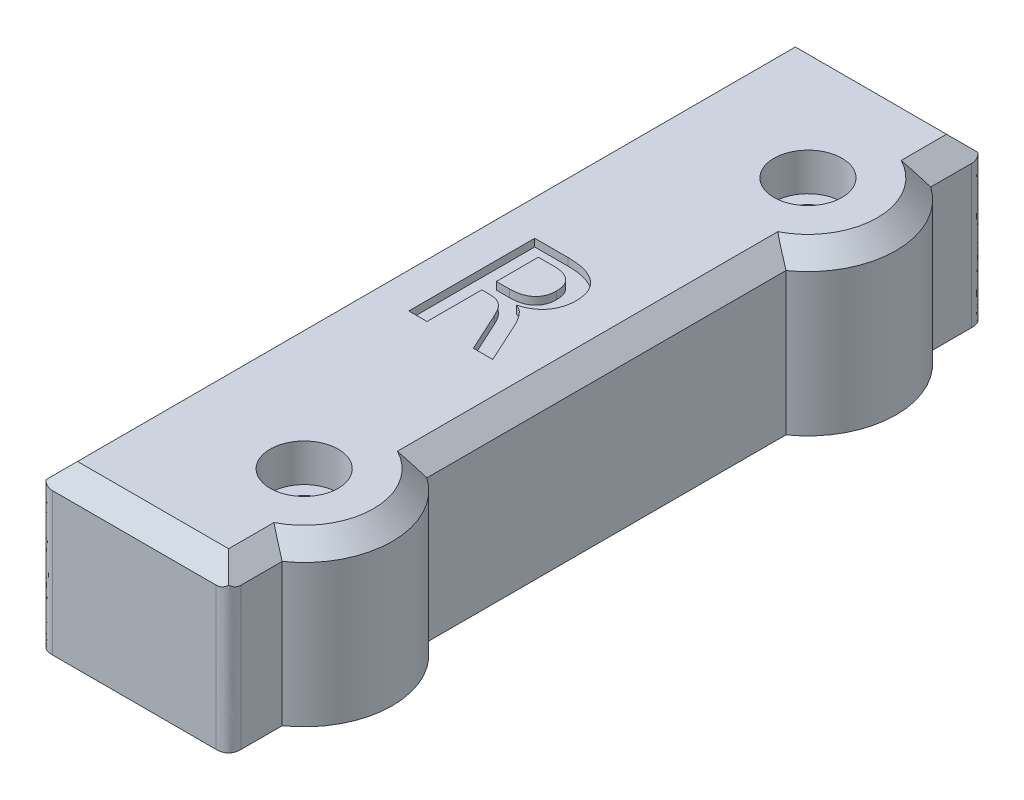
SolidWorks part; units mm, degrees
ref_plane "Front Plane" through (0, 0, 0) normal (0, 0, 1) x (1, 0, 0)
ref_plane "Top Plane" through (0, 0, 0) normal (0, 1, 0) x (1, 0, 0)
ref_plane "Right Plane" through (0, 0, 0) normal (1, 0, 0) x (0, 0, -1)
sketch "Sketch1" plane through (0, 0, 0) normal (0, 1, 0) x (1, 0, 0)
  line L0 (-1.3042, 0) -> (2.0884, 0) construction
  line L1 (0, -3.051) -> (0, -13.887) construction
  line L2 (7.5, 20) -> (-7.5, 20) construction
  line L3 (7.5, -30) -> (-7.5, -30)
  line L4 (7.5, -30) -> (7.5, 30)
  line L5 (7.5, 30) -> (-7.5, 30)
  line L6 (-7.5, -30) -> (-7.5, 30)
  line L7 (7.5, -30) -> (-7.5, 30) construction
  line L8 (7.5, 30) -> (-7.5, -30) construction
  line L9 (7.5, -20) -> (-7.5, -20) construction
  circle A6 centre (3.5, 20) radius 1.65
  circle A7 centre (3.5, -20) radius 1.65
  point P3 (0, 0)
  dimension "D4" = 3.3
  dimension "D1" = 10
  dimension "D2" = 40
  dimension "D3" = 15
  dimension "D5" = 4
extrude "Boss-Extrude1" add sketch "Sketch1" along normal blind 12.8
sketch "Sketch5" plane through (0, 0, 0) normal (0, -1, 0) x (1, 0, 0)
  line L0 (7.5, -30) -> (-7.5, -30) construction
  line L1 (-7.5, -10.5) -> (5.5, -10.5)
  line L2 (-7.5, -10.5) -> (-7.5, 2.5)
  line L3 (-7.5, 2.5) -> (5.5, 2.5)
  line L4 (5.5, -10.5) -> (5.5, 2.5)
  line L5 (-7.5, -30) -> (-7.5, 30) construction
  dimension "D1" = 13
  dimension "D2" = 13
  dimension "D3" = 19.5
extrude "Cut-Extrude3" cut sketch "Sketch5" against normal blind 8 and the other way through all
sketch "Sketch6" plane through (0, 8, 0) normal (0, -1, 0) x (1, 0, 0)
  line L0 (-7.5, -4) -> (5.5, -4) construction
  line L1 (-7.5, 2.5) -> (-7.5, -10.5) construction
  line L2 (5.5, -10.5) -> (5.5, 2.5) construction
  circle A0 centre (-2.5, -0.75) radius 1.45
  circle A1 centre (-2.5, -7.25) radius 1.45
  dimension "D1" = 2.9
  dimension "D2" = 5
  dimension "D3" = 6.5
extrude "Cut-Extrude4" cut sketch "Sketch6" against normal blind 3
sketch "Sketch8" plane through (0, 12.8, 0) normal (0, 1, 0) x (1, 0, 0)
  circle A0 centre (3.5, 20) radius 2.7
  circle A1 centre (3.5, -20) radius 2.7
  dimension "D1" = 5.4
extrude "Cut-Extrude6" cut sketch "Sketch8" against normal blind 3
sketch "Sketch9" plane through (0, 0, 0) normal (0, -1, 0) x (1, 0, 0)
  line L6 (-7.5, -10.5) -> (5.5, -10.5) construction
  line L7 (-2.5, -10.5) -> (1.5, -10.5)
  line L8 (-2.5, -10.5) -> (-2.5, -30)
  line L9 (-2.5, -30) -> (1.5, -30)
  line L10 (1.5, -10.5) -> (1.5, -30)
  line L11 (7.5, -30) -> (-7.5, -30) construction
  circle A0 centre (3.5, -20) radius 1.65 construction
  dimension "D3" = 4
  dimension "D4" = 2
extrude "Cut-Extrude9" cut sketch "Sketch9" against normal blind 2
sketch "Sketch11" plane through (-7.5, 0, 0) normal (-1, 0, 0) x (0, 0, 1)
  line L0 (0, 0) -> (0, 8.8) construction
  line L12 (-20, 0.075) -> (-20, 11.875) construction
  line L14 (20, 0.075) -> (20, 8.875) construction
  line L15 (2.5, 0) -> (30, 0) construction
  line L17 (13.8, 0) -> (26.2, 0)
  line L18 (13.8, 0) -> (13.8, 8.4)
  line L19 (13.8, 8.4) -> (26.2, 8.4)
  line L20 (26.2, 0) -> (26.2, 8.4)
  line L21 (13.8, 0) -> (26.2, 8.4) construction
  line L22 (13.8, 8.4) -> (26.2, 0) construction
  line L29 (-30, 0) -> (-10.5, 0) construction
  line L30 (-26.2, 0) -> (-13.8, 0)
  line L31 (-26.2, 0) -> (-26.2, 8.4)
  line L32 (-26.2, 8.4) -> (-13.8, 8.4)
  line L33 (-13.8, 0) -> (-13.8, 8.4)
  line L34 (-26.2, 0) -> (-13.8, 8.4) construction
  line L35 (-26.2, 8.4) -> (-13.8, 0) construction
  point P5 (-20, 4.2)
  point P20 (20, 4.2)
  dimension "D1" = 12.4
  dimension "D2" = 20
  dimension "D3" = 20
  dimension "D5" = 8.4
extrude "Cut-Extrude11" cut sketch "Sketch11" against normal blind 3
fillet "Fillet1" radius 0.5 4 edges at (-6, 8.4, 26.2) (-6, 8.4, 13.8) (-6, 8.4, -13.8) (-6, 8.4, -26.2)
sketch "Sketch12" plane through (0, 12.8, 0) normal (0, 1, 0) x (1, 0, 0)
  line L0 (0, 30) -> (0, -30) construction
  line L1 (7.5, 30) -> (-7.5, 30) construction
  line L2 (-7.5, -30) -> (7.5, -30) construction
  line L3 (-7.5, 0) -> (7.5, 0) construction
  line L4 (-7.5, 30) -> (-7.5, -30) construction
  line L5 (7.5, -30) -> (7.5, 30) construction
  text T0 "R" font "Consolas" height 10
  dimension "D1" = 4.5
  dimension "D2" = 5
extrude "Cut-Extrude12" cut sketch "Sketch12" against normal blind 0.6
sketch "Sketch13" plane through (0, 0, 0) normal (0, 1, 0) x (1, 0, 0)
  line L0 (-12.8001, 0) -> (14.3011, 0) construction
  line L1 (7.5, -30) -> (7.5, 30) construction
  line L2 (7.5, 25.7446) -> (7.5, 14.2554)
  line L3 (7.5, -25.7446) -> (7.5, -14.2554)
  arc A0 (7.5, 25.7446) -> (7.5, 14.2554) centre (3.5, 20) cw
  arc A1 (7.5, -25.7446) -> (7.5, -14.2554) centre (3.5, -20) ccw
  dimension "D1" = 7
extrude "Boss-Extrude2" add sketch "Sketch13" along normal up to surface (12.8 mm away) up to face at (0, 12.8, 0)
chamfer "Chamfer1" distance 1.5 angle 45 8 edges at (0, 12.8, -30) (7.5, 12.8, -27.8723) (10.5, 12.8, -20) (7.5, 12.8, 0) (10.5, 12.8, 20) (7.5, 12.8, 27.8723) (0, 12.8, 30) (-7.5, 12.8, 0)
fillet "Fillet2" radius 1 4 edges at (-7.5, 5.65, -30) (7.5, 5.65, -30) (7.5, 5.65, 30) (-7.5, 5.65, 30) conic rho 0.5
chamfer "Chamfer2" distance 0.6 angle 45 2 edges at (-2.5, 8, -2.2) (-2.5, 8, -5.8)
